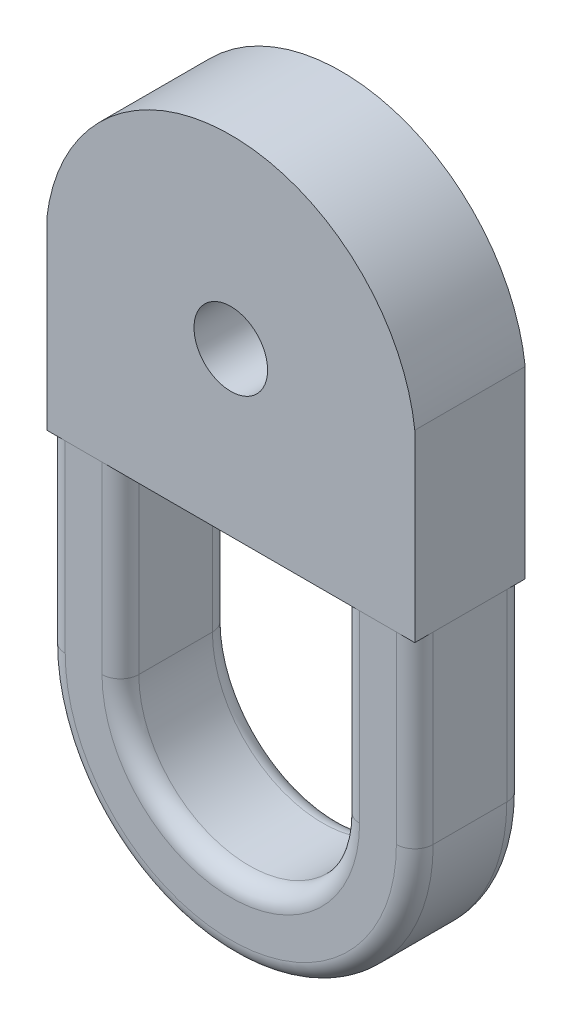
SolidWorks part; units mm, degrees
material "1060 Alloy"
ref_plane "Front Plane" through (0, 0, 0) normal (0, 0, 1) x (1, 0, 0)
ref_plane "Top Plane" through (0, 0, 0) normal (0, 1, 0) x (1, 0, 0)
ref_plane "Right Plane" through (0, 0, 0) normal (1, 0, 0) x (0, 0, -1)
sketch "Sketch1" plane through (0, 0, 0) normal (0, 0, 1) x (1, 0, 0)
  line L0 (0, 0) -> (0, 5)
  line L1 (5, 9.4479) -> (5, -31.1921) construction
  line L2 (10, 5) -> (10, 0)
  line L3 (10, 0) -> (0, 0)
  arc A0 (0, 5) -> (10, 5) centre (5, 4.4137) cw
  circle A1 centre (5, 4.4137) radius 1
  dimension "D2" = 2
  dimension "D1" = 40.64
  dimension "D3" = 10
  dimension "D4" = 5
  dimension "D5" = 0
extrude "Boss-Extrude1" add sketch "Sketch1" along normal blind 3
sketch "Sketch2" plane through (0, 0, 3) normal (0, 0, 1) x (1, 0, 0)
  line L0 (0, 0) -> (10, 0)
  line L1 (0, 0) -> (0, -5)
  line L2 (10, 0) -> (10, -5)
  line L3 (2, -5) -> (2, 0)
  line L4 (8, -5) -> (8, 0)
  line L5 (10, 0) -> (10, 5) construction
  circle A0 centre (5, -5) radius 5
  circle A1 centre (5, -5) radius 3
  line M9 (0, 0) -> (10, 0)
  dimension "D1" = 2
  dimension "D3" = 2
  dimension "D2" = 2
  dimension "D4" = 0
extrude "Boss-Extrude2" add sketch "Sketch2" against normal blind 3 separate body contours A1 L3 A0 L4 | A0 L3 L1 M9 | A0 L2 L4 M9 region at (0.7661, -1.2953, 3) region at (0.6482, -2.8241, 3) region at (9.2339, -1.2953, 3)
fillet "Fillet7" radius 0.5 12 edges at (8, -2.5, 0) (5, -8, 0) (8, -2.5, 3) (5, -8, 3) (0, -2.5, 0) (10, -2.5, 0) (10, -2.5, 3) (5, -10, 3) (2, -2.5, 0) (2, -2.5, 3) (5, -10, 0) (0, -2.5, 3)
